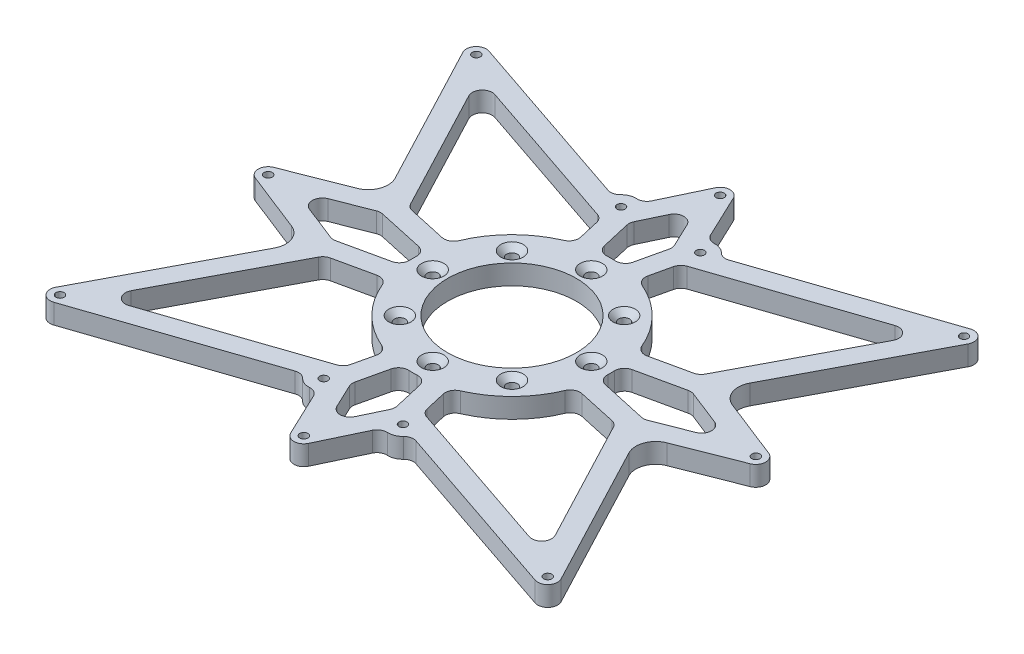
SolidWorks part; units mm, degrees
material "Thornel Mat VMA"
ref_plane "前视基准面" through (0, 0, 0) normal (0, 0, 1) x (1, 0, 0)
ref_plane "上视基准面" through (0, 0, 0) normal (0, 1, 0) x (1, 0, 0)
ref_plane "右视基准面" through (0, 0, 0) normal (1, 0, 0) x (0, 0, -1)
sketch "草图1" plane through (0, 0, 0) normal (0, 1, 0) x (1, 0, 0)
  line L0 (-4.5175, 107.1429) -> (-45.1754, 21.4286)
  line L1 (-123, 105) -> (123, 105) construction
  line L2 (-123, 105) -> (-123, -105) construction
  line L3 (-123, -105) -> (123, -105) construction
  line L4 (123, 105) -> (123, -105) construction
  line L5 (-123, 105) -> (123, -105) construction
  line L6 (-123, -105) -> (123, 105) construction
  line L7 (0, 105) -> (0, -105) construction
  line L8 (123, 0) -> (-123, 0) construction
  line L9 (4.5175, 107.1429) -> (45.1754, 21.4286)
  line L10 (-4.5175, -107.1429) -> (-45.1754, -21.4286)
  line L11 (4.5175, -107.1429) -> (45.1754, -21.4286)
  line L12 (-124.8293, 4.6534) -> (-18.2927, 46.5336)
  line L13 (-124.8293, -4.6534) -> (-18.2927, -46.5336)
  line L14 (124.8293, -4.6534) -> (18.2927, -46.5336)
  line L15 (124.8293, 4.6534) -> (18.2927, 46.5336)
  line L16 (121.3963, 109.7358) -> (-27.1487, 59.4322)
  line L17 (127.4255, 102.673) -> (56.9631, -31.332)
  line L18 (-121.3963, 109.7358) -> (27.1487, 59.4322)
  line L19 (-127.4255, 102.673) -> (-56.9631, -31.332)
  line L20 (127.4255, -102.673) -> (56.9631, 31.332)
  line L21 (121.3963, -109.7358) -> (-27.1487, -59.4322)
  line L22 (-127.4255, -102.673) -> (-56.9631, 31.332)
  line L23 (-121.3963, -109.7358) -> (27.1487, -59.4322)
  circle A0 centre (-123, 0) radius 2.05
  circle A1 centre (-123, 105) radius 2.05
  circle A2 centre (123, 105) radius 2.05
  circle A3 centre (123, 0) radius 2.05
  circle A4 centre (123, -105) radius 2.05
  circle A5 centre (-123, -105) radius 2.05
  circle A6 centre (123, 105) radius 5
  circle A7 centre (123, 0) radius 5
  circle A8 centre (123, -105) radius 5
  circle A9 centre (-123, -105) radius 5
  circle A10 centre (-123, 0) radius 5
  circle A11 centre (-123, 105) radius 5
  circle A12 centre (0, 105) radius 5
  circle A13 centre (0, 105) radius 2.05
  circle A14 centre (0, -105) radius 5
  circle A15 centre (0, -105) radius 2.05
  circle A16 centre (0, 0) radius 50
  circle A17 centre (0, 0) radius 65
  point P0 (0, 0)
  point P6 (-123, 0)
  point P7 (123, 0)
  point P22 (0, 105)
  point P23 (0, -105)
  dimension "D3" = 4.1
  dimension "D4" = 10
  dimension "D5" = 100
  dimension "D1" = 246
  dimension "D2" = 210
  dimension "D6" = 15
extrude "凸台-拉伸1" add sketch "草图1" along normal blind 10 contours A17 L0 L18 A11 L19 L12 | A10 L13 L22 L19 L12 | A17 L13 L22 A9 L23 L10 | A14 L11 L21 L23 L10 | A17 L11 L21 A8 L20 L14 | A7 L15 L17 L20 L14 | A17 L15 L17 A6 L16 L9 | A12 L0 L18 L16 L9 | L16 L18 L9 | L18 L0 L16 | L20 L17 L15 | L14 L20 L17 | A17 L17 L20 | A17 L18 L16 | L19 L22 L12 | L22 L13 L19 | A17 L22 L19 | L10 L23 L21 | A17 L21 L23 | L23 L21 L11 | L14 A17 L15 L9 A16 L11 | L15 A17 L9 | L9 A17 L0 L12 A16 L15 | A16 L9 L15 | L0 A17 L12 | A16 L12 L0 | L12 A17 L13 L10 A16 L0 | L13 A17 L10 | A16 L10 L13 | A17 L11 L14 A16 L13 L10 | L11 A17 L14 | A16 L14 L11 | A17 L10 L21 | A17 L23 L11 | A17 L16 L0 | A17 L9 L18 | A9 | A10 | A11 | A12 | A6 | A7 | A8 | A14 region at (0, 0, -84.4313) region at (-15.5942, 0, -67.7776) region at (-75.1951, 0, -66.6842) region at (-25.6679, 0, -59.8145) region at (0, 0, -65.7493) region at (15.5942, 0, -67.7776) region at (75.1951, 0, -66.6842) region at (0, 0, -53.9943) region at (-41.2892, 0, -44.2129) region at (25.6679, 0, -59.8145) region at (-34.6638, 0, -37.1183) region at (-53.281, 0, 0) region at (-95.568, 0, 0) region at (-71.5567, 0, -17.31) region at (41.2892, 0, -44.2129) region at (-66.8102, 0, 0) region at (-71.5567, 0, 17.31) region at (53.281, 0, 0) region at (34.6638, 0, -37.1183) region at (71.5567, 0, -17.31) region at (95.568, 0, 0) region at (-34.6638, 0, 37.1183) region at (-75.1951, 0, 66.6842) region at (66.8102, 0, 0) region at (71.5567, 0, 17.31) region at (0, 0, 53.9943) region at (-41.2892, 0, 44.2129) region at (75.1951, 0, 66.6842) region at (-25.6679, 0, 59.8145) region at (34.6638, 0, 37.1183) region at (41.2892, 0, 44.2129) region at (-15.5942, 0, 67.7776) region at (0, 0, 65.7493) region at (0, 0, 84.4313) region at (25.6679, 0, 59.8145) region at (15.5942, 0, 67.7776)
extrude "切除-拉伸1" cut sketch "草图1<3>" against normal through all and the other way through all contours A13 | A1 | A0 | A5 | A15 | A4 | A3 | A2 region at (-123, 0, 0) region at (-123, 0, -105) region at (123, 0, -105) region at (123, 0, 0) region at (123, 0, 105) region at (-123, 0, 105) region at (0, 0, -105) region at (0, 0, 105)
sketch "草图1<3>" plane through (0, 0, 0) normal (0, 1, 0) x (1, 0, 0) same geometry as "草图1"
sketch "草图3" plane through (0, 10, 0) normal (0, 1, 0) x (1, 0, 0)
  circle A0 centre (0, 0) radius 32.5
  circle A1 centre (0, 0) radius 40 construction
  circle A2 centre (0, 40) radius 2.55
  circle A3 centre (28.2843, 28.2843) radius 2.55
  circle A4 centre (40, 0) radius 2.55
  circle A5 centre (28.2843, -28.2843) radius 2.55
  circle A6 centre (0, -40) radius 2.55
  circle A7 centre (-28.2843, -28.2843) radius 2.55
  circle A8 centre (-40, 0) radius 2.55
  circle A9 centre (-28.2843, 28.2843) radius 2.55
  circle A10 centre (0, 0) radius 50.5
  point P22 (0, 0)
  dimension "D1" = 65
  dimension "D2" = 80
  dimension "D3" = 5.1
  dimension "D5" = 101
  dimension "D4" = 8
extrude "凸台-拉伸2" add sketch "草图3" against normal up to surface (10 mm away) up to face at (123, 0, -102.95)
sketch "草图2" plane through (0, 10, 0) normal (0, 1, 0) x (1, 0, 0)
  line L0 (-14.4126, 62.9488) -> (-112.75, 96.25)
  line L1 (-112.75, 96.25) -> (-70.2239, 15.3742)
  line L2 (-70.2239, 15.3742) -> (-109.3333, 0)
  line L3 (-109.3333, 0) -> (-70.2239, -15.3742)
  line L4 (-70.2239, -15.3742) -> (-112.75, -96.25)
  line L5 (-112.75, -96.25) -> (-14.4126, -62.9488)
  line L6 (-14.4126, -62.9488) -> (0, -93.3333)
  line L7 (0, -93.3333) -> (14.4126, -62.9488)
  line L8 (14.4126, -62.9488) -> (112.75, -96.25)
  line L9 (112.75, -96.25) -> (70.2239, -15.3742)
  line L10 (70.2239, -15.3742) -> (109.3333, 0)
  line L11 (109.3333, 0) -> (70.2239, 15.3742)
  line L12 (70.2239, 15.3742) -> (112.75, 96.25)
  line L13 (112.75, 96.25) -> (14.4126, 62.9488)
  line L14 (14.4126, 62.9488) -> (0, 93.3333)
  line L15 (0, 93.3333) -> (-14.4126, 62.9488)
  line L16 (121.3963, 109.7358) -> (19.6339, 75.2748)
  line L17 (19.6339, 75.2748) -> (4.5175, 107.1429)
  line L18 (-4.5175, 107.1429) -> (-19.6339, 75.2748)
  line L19 (-19.6339, 75.2748) -> (-121.3963, 109.7358)
  line L20 (-127.4255, 102.673) -> (-84.2689, 20.5979)
  line L21 (-84.2689, 20.5979) -> (-124.8293, 4.6534)
  line L22 (-124.8293, -4.6534) -> (-84.2689, -20.5979)
  line L23 (-84.2689, -20.5979) -> (-127.4255, -102.673)
  line L24 (-121.3963, -109.7358) -> (-19.6339, -75.2748)
  line L25 (-19.6339, -75.2748) -> (-4.5175, -107.1429)
  line L26 (4.5175, -107.1429) -> (19.6339, -75.2748)
  line L27 (19.6339, -75.2748) -> (121.3963, -109.7358)
  line L28 (127.4255, -102.673) -> (84.2689, -20.5979)
  line L29 (84.2689, -20.5979) -> (124.8293, -4.6534)
  line L30 (124.8293, 4.6534) -> (84.2689, 20.5979)
  line L31 (84.2689, 20.5979) -> (127.4255, 102.673)
  line L32 (121.3963, 109.7358) -> (19.6339, 75.2748)
  line L33 (19.6339, 75.2748) -> (4.5175, 107.1429)
  line L34 (-4.5175, 107.1429) -> (-19.6339, 75.2748)
  line L35 (-19.6339, 75.2748) -> (-121.3963, 109.7358)
  line L36 (-127.4255, 102.673) -> (-84.2689, 20.5979)
  line L37 (-84.2689, 20.5979) -> (-124.8293, 4.6534)
  line L38 (-124.8293, -4.6534) -> (-84.2689, -20.5979)
  line L39 (-84.2689, -20.5979) -> (-127.4255, -102.673)
  line L40 (-121.3963, -109.7358) -> (-19.6339, -75.2748)
  line L41 (-19.6339, -75.2748) -> (-4.5175, -107.1429)
  line L42 (4.5175, -107.1429) -> (19.6339, -75.2748)
  line L43 (19.6339, -75.2748) -> (121.3963, -109.7358)
  line L44 (127.4255, -102.673) -> (84.2689, -20.5979)
  line L45 (84.2689, -20.5979) -> (124.8293, -4.6534)
  line L46 (124.8293, 4.6534) -> (84.2689, 20.5979)
  line L47 (84.2689, 20.5979) -> (127.4255, 102.673)
  line L48 (-70.2239, 15.3742) -> (0, 0)
  line L49 (0, 0) -> (-70.2239, -15.3742)
  line L50 (70.2239, 15.3742) -> (0, 0)
  line L51 (70.2239, -15.3742) -> (0, 0)
  line L52 (-96.1429, 15.9302) -> (-1.0693, -4.8843)
  line L53 (-1.0693, 4.8843) -> (-96.1429, -15.9302)
  line L54 (86.0334, 23.9538) -> (-1.0693, 4.8843)
  line L55 (96.1429, -15.9302) -> (1.0693, 4.8843)
  line L56 (-86.0334, 23.9538) -> (1.0693, 4.8843)
  line L57 (1.0693, -4.8843) -> (-86.0334, -23.9538)
  line L58 (96.1429, 15.9302) -> (1.0693, -4.8843)
  line L59 (86.0334, -23.9538) -> (-1.0693, -4.8843)
  line L60 (69.1546, 20.2585) -> (-1.0693, 4.8843) construction
  line L61 (71.2933, 10.4899) -> (1.0693, -4.8843) construction
  line L62 (71.2933, -10.4899) -> (1.0693, 4.8843) construction
  line L63 (69.1546, -20.2585) -> (-1.0693, -4.8843) construction
  line L64 (-1.0693, 4.8843) -> (-71.2933, -10.4899) construction
  line L65 (1.0693, -4.8843) -> (-69.1546, -20.2585) construction
  line L66 (-71.2933, 10.4899) -> (-1.0693, -4.8843) construction
  line L67 (-69.1546, 20.2585) -> (1.0693, 4.8843) construction
  line L68 (-14.4126, -62.9488) -> (0, 0)
  line L69 (14.4126, -62.9488) -> (0, 0)
  line L70 (0, 0) -> (-14.4126, 62.9488)
  line L71 (14.4126, 62.9488) -> (0, 0)
  line L72 (-23.8821, -81.9047) -> (-4.8739, 1.1159)
  line L73 (14.5563, -85.9793) -> (-4.8739, -1.1159)
  line L74 (-4.8739, -1.1159) -> (-21.6277, 72.0582)
  line L75 (21.9453, 73.4454) -> (4.8739, -1.1159)
  line L76 (-13.6257, -81.915) -> (4.8739, -1.1159)
  line L77 (23.8857, -81.9201) -> (4.8739, 1.1159)
  line L78 (4.8739, 1.1159) -> (-12.4369, 76.7228)
  line L79 (12.1113, 75.3004) -> (-4.8739, 1.1159)
  line L80 (9.5388, 64.0647) -> (-4.8739, 1.1159) construction
  line L81 (19.2865, 61.8329) -> (4.8739, -1.1159) construction
  line L82 (4.8739, 1.1159) -> (-9.5388, 64.0647) construction
  line L83 (-4.8739, -1.1159) -> (-19.2865, 61.8329) construction
  line L84 (-19.2865, -61.8329) -> (-4.8739, 1.1159) construction
  line L85 (-9.5388, -64.0647) -> (4.8739, -1.1159) construction
  line L86 (9.5388, -64.0647) -> (-4.8739, -1.1159) construction
  line L87 (19.2865, -61.8329) -> (4.8739, 1.1159) construction
  circle A1 centre (0, 0) radius 50
  arc A2 (-112.75, 96.25) -> (-112.75, 96.25) centre (-112.75, 96.25) ccw
  arc A3 (-109.3333, 0) -> (-109.3333, 0) centre (-109.3333, 0) ccw
  arc A4 (-112.75, -96.25) -> (-112.75, -96.25) centre (-112.75, -96.25) ccw
  arc A5 (0, -93.3333) -> (0, -93.3333) centre (0, -93.3333) ccw
  arc A6 (112.75, -96.25) -> (112.75, -96.25) centre (112.75, -96.25) ccw
  arc A7 (109.3333, 0) -> (109.3333, 0) centre (109.3333, 0) ccw
  arc A8 (112.75, 96.25) -> (112.75, 96.25) centre (112.75, 96.25) ccw
  arc A9 (0, 93.3333) -> (0, 93.3333) centre (0, 93.3333) ccw
  arc A10 (4.5175, 107.1429) -> (-4.5175, 107.1429) centre (0, 105) ccw
  arc A11 (-121.3963, 109.7358) -> (-127.4255, 102.673) centre (-123, 105) ccw
  arc A12 (-124.8293, 4.6534) -> (-124.8293, -4.6534) centre (-123, 0) ccw
  arc A13 (-127.4255, -102.673) -> (-121.3963, -109.7358) centre (-123, -105) ccw
  arc A14 (-4.5175, -107.1429) -> (4.5175, -107.1429) centre (0, -105) ccw
  arc A15 (121.3963, -109.7358) -> (127.4255, -102.673) centre (123, -105) ccw
  arc A16 (124.8293, -4.6534) -> (124.8293, 4.6534) centre (123, 0) ccw
  arc A17 (127.4255, 102.673) -> (121.3963, 109.7358) centre (123, 105) ccw
  arc A18 (4.5175, 107.1429) -> (-4.5175, 107.1429) centre (0, 105) ccw
  arc A19 (-121.3963, 109.7358) -> (-127.4255, 102.673) centre (-123, 105) ccw
  arc A20 (-124.8293, 4.6534) -> (-124.8293, -4.6534) centre (-123, 0) ccw
  arc A21 (-127.4255, -102.673) -> (-121.3963, -109.7358) centre (-123, -105) ccw
  arc A22 (-4.5175, -107.1429) -> (4.5175, -107.1429) centre (0, -105) ccw
  arc A23 (121.3963, -109.7358) -> (127.4255, -102.673) centre (123, -105) ccw
  arc A24 (124.8293, -4.6534) -> (124.8293, 4.6534) centre (123, 0) ccw
  arc A25 (127.4255, 102.673) -> (121.3963, 109.7358) centre (123, 105) ccw
  dimension "D1" = 100
  dimension "D2" = 0
  dimension "D3" = 10
  dimension "D4" = 5
  dimension "D5" = 5
  dimension "D6" = 5
  dimension "D7" = 5
extrude "切除-拉伸2" cut sketch "草图2" against normal through all contours A1 L0 L1 L56 | A1 L54 L12 L13 | A1 L14 L15 | A1 L55 L10 L11 L58 | A1 L8 L9 L59 | A1 L6 L7 | A1 L57 L4 L5 | A1 L52 L2 L3 L53 region at (-62.3632, 10, -55.1889) region at (0, 10, -68.0759) region at (-75.5405, 10, 0) region at (62.3632, 10, -55.1889) region at (-62.3632, 10, 55.1889) region at (75.5405, 10, 0) region at (62.3632, 10, 55.1889) region at (0, 10, 68.0759)
fillet "圆角2" radius 10 8 edges at (84.2689, 5, -20.5979) (84.2689, 5, 20.5979) (19.6339, 5, 75.2748) (-19.6339, 5, 75.2748) (-84.2689, 5, 20.5979) (-84.2689, 5, -20.5979) (-19.6339, 5, -75.2748) (19.6339, 5, -75.2748)
fillet "圆角3" radius 5 40 edges at (15.9771, 5, -47.3786) (19.9732, 5, -64.8318) (112.75, 5, -96.25) (73.2654, 5, -21.1585) (47.529, 5, -15.524) (49.6677, 5, -5.7553) (78.5869, 5, -12.0866) (109.3333, 5, 0) (78.5869, 5, 12.0866) (49.6677, 5, 5.7553) (6.2293, 5, 49.6104) (10.9531, 5, 70.2421) (0, 5, 93.3333) (-10.9531, 5, 70.2421) (-6.2293, 5, 49.6104) (-49.6677, 5, 5.7553) (-78.5869, 5, 12.0866) (-109.3333, 5, 0) (-78.5869, 5, -12.0866) (-49.6677, 5, -5.7553) (-47.529, 5, -15.524) (-73.2654, 5, -21.1585) (-112.75, 5, -96.25) (-19.9732, 5, -64.8318) (-15.9771, 5, -47.3786) (-15.9771, 5, 47.3786) (-19.9732, 5, 64.8318) (-112.75, 5, 96.25) (-73.2654, 5, 21.1585) (-47.529, 5, 15.524) (47.529, 5, 15.524) (73.2654, 5, 21.1585) (112.75, 5, 96.25) (19.9732, 5, 64.8318) (15.9771, 5, 47.3786) (-6.2293, 5, -49.6104) (-10.9531, 5, -70.2421) (0, 5, -93.3333) (10.9531, 5, -70.2421) (6.2293, 5, -49.6104)
sketch "草图4" plane through (0, 10, 0) normal (0, 1, 0) x (1, 0, 0)
  line L1 (-20, 75) -> (20, 75) construction
  line L2 (-20, 75) -> (-20, -75) construction
  line L3 (-20, -75) -> (20, -75) construction
  line L4 (20, 75) -> (20, -75) construction
  line L5 (-20, 75) -> (20, -75) construction
  line L6 (-20, -75) -> (20, 75) construction
  circle A0 centre (-20, -75) radius 2.05
  circle A1 centre (20, -75) radius 2.05
  circle A2 centre (-20, 75) radius 2.05
  circle A3 centre (20, 75) radius 2.05
  point P0 (0, 0)
  dimension "D3" = 4.1
  dimension "D1" = 150
  dimension "D2" = 40
extrude "切除-拉伸3" cut sketch "草图4" against normal through all
sketch "草图5" plane through (0, 10, 0) normal (0, 1, 0) x (1, 0, 0)
  circle A0 centre (20, 75) radius 7.5
  circle A1 centre (-20, 75) radius 7.5
  circle A2 centre (-20, -75) radius 7.5
  circle A3 centre (20, -75) radius 7.5
  circle A4 centre (20, -75) radius 2.05 construction
  circle A5 centre (-20, -75) radius 2.05 construction
  circle A6 centre (20, 75) radius 2.05 construction
  circle A7 centre (-20, 75) radius 2.05 construction
  circle A8 centre (20, -75) radius 2.05
  circle A9 centre (-20, -75) radius 2.05
  circle A10 centre (20, 75) radius 2.05
  circle A11 centre (-20, 75) radius 2.05
  dimension "D1" = 15
extrude "凸台-拉伸4" add sketch "草图5" against normal up to surface (10 mm away) up to face at (20, 0, 77.05)
fillet "圆角4" radius 5 8 edges at (-26.9487, 5, 77.8224) (-26.9487, 5, -77.8224) (-16.7416, 5, -81.7552) (16.7416, 5, -81.7552) (26.9487, 5, -77.8224) (26.9487, 5, 77.8224) (16.7416, 5, 81.7552) (-16.7416, 5, 81.7552)
hole_wizard "M5 六角凹锥坑螺钉的锥形沉头孔1" positions "草图6" profile "草图7" countersink size "M5" standard "ISO" end condition through all
sketch "草图6" plane through (0, 10, 0) normal (0, 1, 0) x (1, 0, 0)
  point P0 (-28.2843, 28.2843)
  point P3 (0, 40)
  point P6 (28.2843, 28.2843)
  point P9 (40, 0)
  point P12 (28.2843, -28.2843)
  point P15 (0, -40)
  point P18 (-28.2843, -28.2843)
  point P21 (-40, 0)
sketch "草图7" plane through (-28.2843, 10, -28.2843) normal (1, 0, 0) x (0, 0, 1)
  line L0 (0, 0) -> (0, 10)
  line L1 (0, 10) -> (2.75, 10)
  line L2 (2.75, 10) -> (2.75, 2.85)
  line L3 (2.75, 2.85) -> (5.6, 0)
  line L5 (5.6, 0) -> (0, 0)
  line L6 (-2.75, 2.85) -> (-5.6, 0) construction
  line L11 (0, -6.35) -> (0, 107.95) construction
  dimension "通孔孔直径" = 5.5
  dimension "通孔孔深度" = 10
  dimension "近端锥形沉头孔直径" = 11.2
  dimension "近端锥形沉头孔角度" = 90
